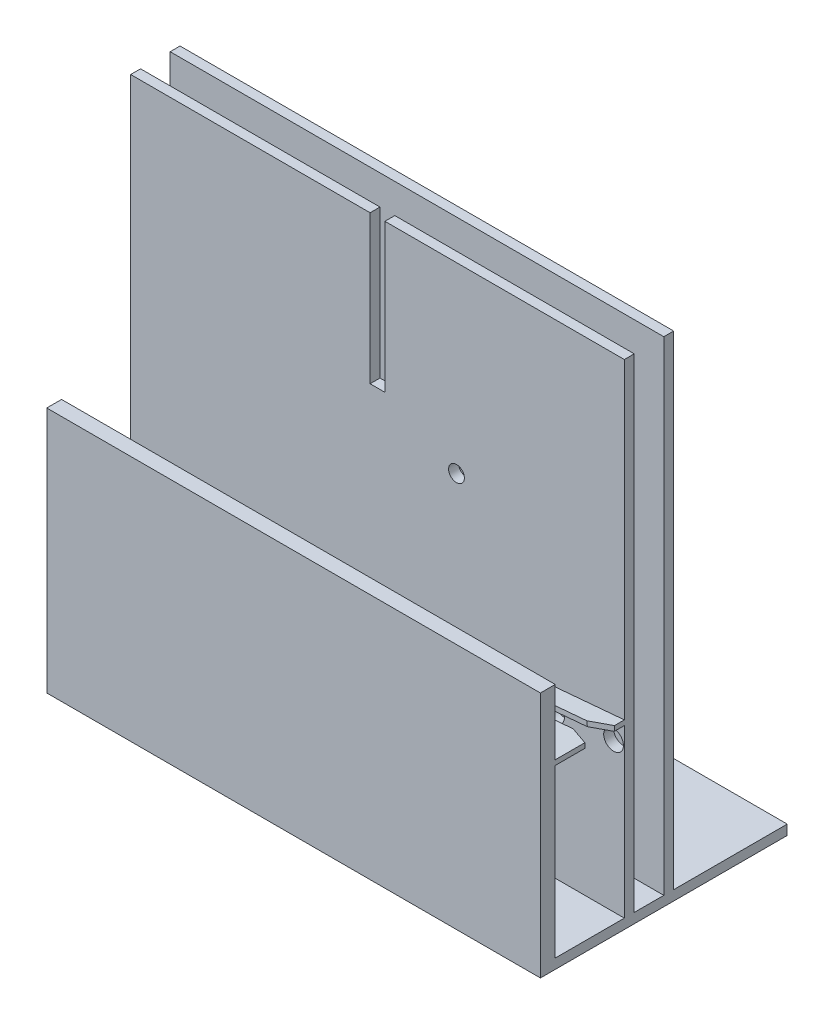
SolidWorks part; units mm, degrees
ref_plane "Front Plane" through (0, 0, 0) normal (0, 0, 1) x (1, 0, 0)
ref_plane "Top Plane" through (0, 0, 0) normal (0, 1, 0) x (1, 0, 0)
ref_plane "Right Plane" through (0, 0, 0) normal (1, 0, 0) x (0, 0, -1)
sketch "Sketch_Machine Case" plane through (0, 0, 0) normal (0, 1, 0) x (1, 0, 0)
  line L0 (-250, 125) -> (250, -125) construction
  line L1 (-250, 125) -> (250, 125)
  line L2 (-250, 125) -> (-250, -125)
  line L3 (-250, -125) -> (250, -125)
  line L4 (250, 125) -> (250, -125)
  dimension "D1" = 500
  dimension "D2" = 250
extrude "Machine Case" add sketch "Sketch_Machine Case" along normal blind 500
sketch "Sketch_Shell" plane through (0, 0, 0) normal (0, 1, 0) x (1, 0, 0)
  line L0 (-250, -125) -> (250, -125) construction
  line L1 (-250, 0) -> (250, 0)
  line L2 (-250, 0) -> (-250, -110)
  line L3 (-250, -110) -> (250, -110)
  line L4 (250, 0) -> (250, -110)
  line L5 (-250, 125) -> (-250, -125) construction
  line L6 (250, -125) -> (250, 125) construction
  line L7 (250, 125) -> (-250, 125) construction
  line L8 (-250, 125) -> (250, 125)
  line L9 (-250, 125) -> (-250, 10)
  line L10 (-250, 10) -> (250, 10)
  line L11 (250, 125) -> (250, 10)
  dimension "D1" = 15
  dimension "D2" = 10
extrude "Cut_Shell" cut sketch "Sketch_Shell" along normal through all from offset 10
sketch "Sketch_Cam Shaft" plane through (0, 0, 0) normal (0, 0, 1) x (1, 0, 0)
  line L0 (0, 0) -> (0, 315) construction
  circle A0 centre (0, 315) radius 15
  dimension "D1" = 30
  dimension "D2" = 315
extrude "Cut_Cam Shaft" cut sketch "Sketch_Cam Shaft" against normal up to next
ref_plane "Plane_Nuzzle Fixture" through (0, 0, 40) normal (0, 0, 1) x (1, 0, 0)
sketch "Sketch_Nuzzle Fixture" plane through (0, 0, 40) normal (0, 0, 1) x (1, 0, 0)
  line L4 (-250, 10) -> (250, 10)
  line L5 (250, 10) -> (250, 500)
  line L6 (250, 500) -> (-250, 500)
  line L7 (-250, 500) -> (-250, 10)
  line L8 (-250, 10) -> (250, 10)
  line L9 (250, 10) -> (250, 500)
  line L10 (250, 500) -> (-250, 500)
  line L11 (-250, 500) -> (-250, 10)
  dimension "D1" = 0
extrude "Nuzzle Fixture" add sketch "Sketch_Nuzzle Fixture" against normal blind 10
sketch "Sketch_Squeezing Slot" plane through (0, 0, 40) normal (0, 0, 1) x (1, 0, 0)
  line L0 (0, 0) -> (0, 500) construction
  line L1 (250, 500) -> (-250, 500) construction
  line L2 (-7.5, 500) -> (7.5, 500)
  line L3 (-7.5, 500) -> (-7.5, 350)
  line L4 (-7.5, 350) -> (7.5, 350)
  line L5 (7.5, 500) -> (7.5, 350)
  dimension "D1" = 15
  dimension "D2" = 150
extrude "Squeezing Slot" cut sketch "Sketch_Squeezing Slot" against normal up to next
sketch "Sketch_Case Trim" plane through (0, 0, 125) normal (0, 0, 1) x (1, 0, 0)
  line L0 (250, 500) -> (250, 0) construction
  line L1 (-250, 500) -> (250, 500)
  line L2 (-250, 500) -> (-250, 250)
  line L3 (-250, 250) -> (250, 250)
  line L4 (250, 500) -> (250, 250)
  point P8 (250, 250)
extrude "Cut_Case Trim" cut sketch "Sketch_Case Trim" against normal up to next
sketch "Sketch_Rolling Wheel Shaft Hole_Inside" plane through (0, 0, 40) normal (0, 0, 1) x (1, 0, 0)
  line L0 (0, 140) -> (0, 0) construction
  circle A0 centre (0, 140) radius 10
  dimension "D1" = 20
  dimension "D2" = 140
extrude "Cut_Rolling Wheel Shaft Hole_Inside" cut sketch "Sketch_Rolling Wheel Shaft Hole_Inside" against normal up to next
sketch "Sketch_Rolling Wheel Shaft Hole_Outside" plane through (0, 0, 110) normal (0, 0, -1) x (-1, 0, 0)
  circle A1 centre (0, 140) radius 10
  circle A2 centre (0, 140) radius 10
  dimension "D1" = 0
extrude "Cut_Rolling Wheel Shaft Hole_Outside" cut sketch "Sketch_Rolling Wheel Shaft Hole_Outside" against normal blind 10
ref_plane "Plane_Mounting Plane" through (0, 335, 0) normal (0, 1, 0) x (1, 0, 0)
sketch "Sketch_Conveyor Slant" plane through (0, 0, 110) normal (0, 0, -1) x (-1, 0, 0)
  line L0 (0, 140) -> (-250, 161.8722) construction
  line L1 (250, 125) -> (-250, 125) construction
  line L2 (250, 250) -> (250, 0) construction
  line L3 (-250, 250) -> (-250, 0) construction
  circle A0 centre (0, 140) radius 10 construction
  dimension "D1" = 5
pattern_linear "LPattern_Conveyor Slant" count 5 spacing 60 along (0.9962, 0.0872, 0) of "Cut_Rolling Wheel Shaft Hole_Outside", "Cut_Rolling Wheel Shaft Hole_Inside"
pattern_linear "LPattern_Conveyor Flat" count 5 spacing 55 along (-1, 0, 0) of "Cut_Rolling Wheel Shaft Hole_Outside", "Cut_Rolling Wheel Shaft Hole_Inside"
sketch "Sketch_Positioning Notch" plane through (0, 0, 40) normal (0, 0, 1) x (1, 0, 0)
  line L0 (250, 171.9104) -> (-0.4366, 150) construction
  line L1 (250, 10) -> (250, 500) construction
  line L2 (-0.4366, 150) -> (-250, 150) construction
  line L3 (-250, 500) -> (-250, 10) construction
  line L4 (250, 178.9104) -> (-0.4366, 157)
  line L5 (-0.4366, 157) -> (-250, 157) construction
  line L6 (250, 183.9104) -> (-0.4366, 162)
  line L7 (-0.4366, 162) -> (-250, 162) construction
  line L8 (-250, 157) -> (-250, 162) construction
  line L9 (250, 250) -> (250, 0) construction
  line L10 (-250, 250) -> (-250, 0) construction
  line L11 (250, 183.9104) -> (250, 178.9104)
  line L12 (-0.4366, 157) -> (-0.4366, 162)
  circle A0 centre (239.0867, 160.9174) radius 10 construction
  circle A2 centre (-220, 140) radius 10 construction
  circle A3 centre (0, 140) radius 10 construction
  circle A4 centre (59.7717, 145.2293) radius 10 construction
  point P28 (-250, 159.5)
  dimension "D1" = 7
  dimension "D2" = 5
extrude "Positioning Notch" add sketch "Sketch_Positioning Notch" along normal up to next
ref_plane "Plane_Notch" through (-14.0688, 160.8073, 0) normal (-0.0872, 0.9962, 0) x (0.9962, 0.0872, 0)
sketch "Sketch_Notch" plane through (-14.0688, 160.8073, 0) normal (-0.0872, 0.9962, 0) x (0.9962, 0.0872, 0)
  line L0 (265.0775, -110) -> (265.0775, -40) construction
  line L1 (13.6843, -58) -> (245.0775, -58)
  line L2 (13.6843, -58) -> (13.6843, -72)
  line L3 (13.6843, -72) -> (245.0775, -72)
  line L4 (245.0775, -58) -> (245.0775, -72) construction
  line L5 (265.0775, -65) -> (13.6843, -65) construction
  line L6 (265.0775, -40) -> (13.6843, -40) construction
  line L7 (13.6843, -110) -> (13.6843, -40) construction
  line L8 (245.0775, -72) -> (265.0775, -80)
  line L9 (265.0775, -80) -> (265.0775, -50)
  line L10 (265.0775, -50) -> (245.0775, -58)
  dimension "D1" = 20
  dimension "D2" = 25
  dimension "D3" = 30
  dimension "D4" = 14
extrude "Cut_Notch" cut sketch "Sketch_Notch" against normal up to next
ref_plane "Plane_Toothbrush Positioning" through (0, 140, 110) normal (0.9962, 0.0872, 0) x (0, 0, -1)
sketch "Sketch_Positioning Pin" plane through (0, 0, 0) normal (0, 0, 1) x (1, 0, 0)
  line L0 (0, 315) -> (0, 150) construction
  circle A0 centre (0, 150) radius 15
  circle A1 centre (0, 315) radius 15 construction
  dimension "D1" = 165
extrude "Cut_Positioning Pin" [suppressed] cut sketch "Sketch_Positioning Pin" against normal up to next
sketch "Sketch_Toothpaste Path Hold" plane through (0, 0, 0) normal (0, 0, 1) x (1, 0, 0)
  line L0 (80, 315) -> (0, 315) construction
  circle A0 centre (80, 315) radius 8
  dimension "D2" = 16
  dimension "D1" = 80
extrude "Cut_Toothpaste Path Hold" cut sketch "Sketch_Toothpaste Path Hold" against normal up to next and the other way up to surface other way up to face at (-45, 140, 40)
equation "\"D1@Machine Case\"=\"D1@Sketch_Machine Case\""
